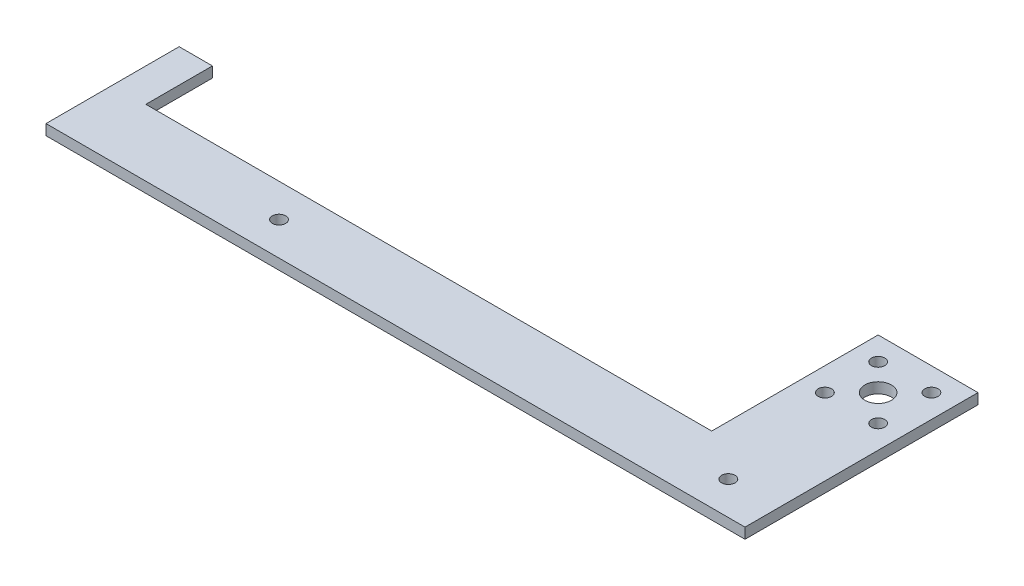
SolidWorks part; units mm, degrees
ref_plane "Front" through (0, 0, 0) normal (0, 0, 1) x (1, 0, 0)
ref_plane "Top" through (0, 0, 0) normal (0, 1, 0) x (1, 0, 0)
ref_plane "Right" through (0, 0, 0) normal (1, 0, 0) x (0, 0, -1)
sketch "Sketch1" plane through (0, 0, 0) normal (0, 1, 0) x (1, 0, 0)
  line L0 (200, -20) -> (200, -40)
  line L1 (0, 0) -> (200, 0)
  line L2 (0, 0) -> (0, -40)
  line L3 (0, -40) -> (200, -40)
  line L4 (200, 0) -> (200, -40)
  line L5 (200, -30) -> (0, -30)
  line L6 (200, -30) -> (185, -30)
  line L7 (185, -30) -> (50, -30)
  line L8 (0, -20) -> (170, -20)
  line L9 (170, -20) -> (170, 0)
  line L10 (200, 0) -> (200, 30)
  line L11 (200, 30) -> (170, 30)
  line L12 (170, 30) -> (170, 0)
  line L13 (200, 0) -> (170, 30)
  line L14 (185, 15) -> (185, 23)
  line L15 (185, 23) -> (193, 23)
  line L16 (193, 23) -> (193, 7)
  line L17 (193, 7) -> (177, 7)
  line L18 (177, 7) -> (177, 23)
  line L19 (177, 23) -> (185, 23)
  line L20 (0, -40) -> (-10, -40)
  line L21 (-10, -40) -> (-10, 0)
  line L22 (-10, 0) -> (0, 0)
  circle A0 centre (50, -30) radius 2
  circle A1 centre (185, -30) radius 2
  circle A2 centre (193, 7) radius 2
  circle A3 centre (177, 7) radius 2
  circle A4 centre (193, 23) radius 2
  circle A5 centre (177, 23) radius 2
  circle A6 centre (185, 15) radius 4
  dimension "D5" = 170
  dimension "D11" = 10
  dimension "D1" = 40
  dimension "D2" = 200
  dimension "D3" = 15
  dimension "D4" = 135
  dimension "D6" = 30
  dimension "D7" = 8
  dimension "D8" = 8
  dimension "D9" = 8
  dimension "D10" = 16
extrude "Boss-Extrude1" add sketch "Sketch1" along normal blind 3.175 contours A5 L18 A3 L17 A2 L13 | A4 L15 L14 L13 A2 L16 | A5 L13 L14 L19 | A5 L13 L12 L1 A2 L17 A3 L18 | A5 L19 L15 A4 L16 A2 L13 L10 L11 | A1 L5 L0 L4 L1 L9 L8 L2 A0 L7 | A1 L7 A0 L5 L2 L3 L4 | L22 L21 L20 L2 region at (119.6257, 0, 21.5015) region at (99.8893, 0, 35.0262) region at (197.5071, 0, -3.0929) region at (185, 0, -0.4243) region at (-5, 0, 20) region at (182.0224, 0, -12.0224) region at (189.9145, 0, -16.9851) region at (182.1671, 0, -20.9553)
